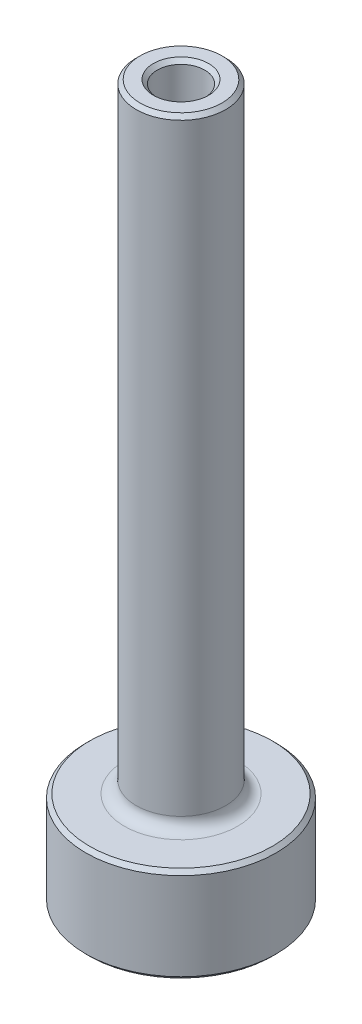
SolidWorks part; units mm, degrees
ref_plane "Front" through (0, 0, 0) normal (0, 0, 1) x (1, 0, 0)
ref_plane "Top" through (0, 0, 0) normal (0, 1, 0) x (1, 0, 0)
ref_plane "Right" through (0, 0, 0) normal (1, 0, 0) x (0, 0, -1)
sketch "Sketch1" plane through (0, 0, 0) normal (0, 0, 1) x (1, 0, 0)
  line L0 (0, 5.5693) -> (0, -5.1628) construction
  line L1 (3.175, 0) -> (6.35, 0)
  line L2 (6.35, 0) -> (6.35, 6.35)
  line L3 (6.35, 6.35) -> (2.9845, 6.35)
  line L4 (2.9845, 6.35) -> (2.9845, 47.625)
  line L5 (2.9845, 47.625) -> (1.5875, 47.625)
  line L6 (1.5875, 47.625) -> (1.5875, 3.175)
  line L7 (1.5875, 3.175) -> (3.175, 3.175)
  line L8 (3.175, 3.175) -> (3.175, 0)
  dimension "D1" = 12.7
  dimension "D2" = 5.969
  dimension "D3" = 3.175
  dimension "D4" = 6.35
  dimension "D5" = 3.175
  dimension "D6" = 3.175
  dimension "D7" = 41.275
revolve "Revolve1" add sketch "Sketch1" angle 360 about L0
sketch "Sketch2" plane through (0, 0, 0) normal (0, -1, 0) x (1, 0, 0)
  line L1 (1.8331, 3.175) -> (-1.8331, 3.175)
  line L2 (-1.8331, 3.175) -> (-3.6662, 0)
  line L3 (-3.6662, 0) -> (-1.8331, -3.175)
  line L4 (-1.8331, -3.175) -> (1.8331, -3.175)
  line L5 (1.8331, -3.175) -> (3.6662, 0)
  line L6 (3.6662, 0) -> (1.8331, 3.175)
  circle A0 centre (0, 0) radius 3.175 construction
  circle A1 centre (0, 0) radius 3.175 construction
extrude "Cut-Extrude1" cut sketch "Sketch2" against normal up to surface (3.175 mm away) up to face at (-3.175, 3.175, 0)
fillet "Fillet1" radius 0.7937 13 edges at (0, 3.175, 3.175) (2.7496, 3.175, 1.5875) (2.7496, 3.175, -1.5875) (0, 3.175, -3.175) (-2.7496, 3.175, -1.5875) (-2.7496, 3.175, 1.5875) (-1.8331, 1.5875, 3.175) (1.8331, 1.5875, 3.175) (3.6662, 1.5875, 0) (1.8331, 1.5875, -3.175) (-1.8331, 1.5875, -3.175) (-3.6662, 1.5875, 0) (-2.9845, 6.35, 0)
chamfer "Chamfer1" distance 0.254 angle 45 17 edges at (-1.5875, 3.175, 0) (-2.9845, 47.625, 0) (-1.5875, 47.625, 0) (-6.35, 0, 0) (-6.35, 6.35, 0) (0, 0, -3.175) (1.7717, 0, -3.0687) (-1.7717, 0, -3.0687) (2.7496, 0, -1.5875) (-2.7496, 0, -1.5875) (3.5434, 0, 0) (-3.5434, 0, 0) (2.7496, 0, 1.5875) (-2.7496, 0, 1.5875) (1.7717, 0, 3.0687) (-1.7717, 0, 3.0687) (0, 0, 3.175)
